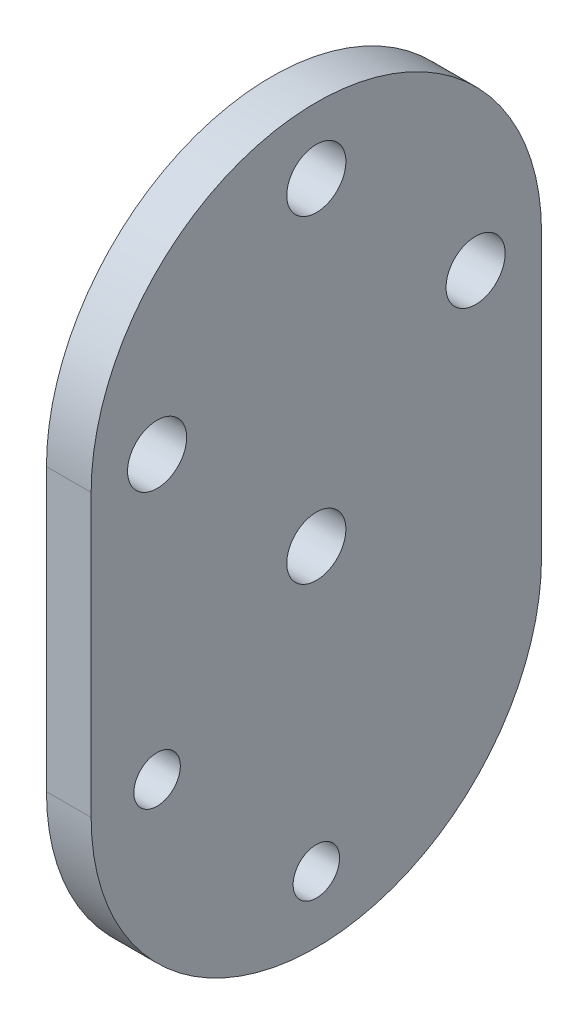
SolidWorks part; units mm, degrees
ref_plane "Front" through (0, 0, 0) normal (0, 0, 1) x (1, 0, 0)
ref_plane "Top" through (0, 0, 0) normal (0, 1, 0) x (1, 0, 0)
ref_plane "Right" through (0, 0, 0) normal (1, 0, 0) x (0, 0, -1)
sketch "Sketch2" plane through (0, 0, 0) normal (1, 0, 0) x (0, 0, -1)
  line L0 (0, -10) -> (0, 10) construction
  line L1 (-16, -10) -> (-16, 10)
  line L2 (16, -10) -> (16, 10)
  arc A0 (-16, -10) -> (16, -10) centre (0, -10) ccw
  arc A1 (16, 10) -> (-16, 10) centre (0, 10) ccw
  circle A2 centre (0, 10) radius 11.3137
  circle A3 centre (0, 21.3137) radius 2.1
  circle A4 centre (0, -1.3137) radius 2.1
  circle A5 centre (11.3137, 10) radius 2.1
  circle A6 centre (-11.3137, 10) radius 2.1
  circle A7 centre (0, -10) radius 11.3137
  circle A8 centre (-11.3137, -10) radius 1.65
  circle A9 centre (0, -21.3137) radius 1.65
  circle A10 centre (11.3137, -10) radius 1.65
  point P2 (0, 0)
extrude "Boss-Extrude1" add sketch "Sketch2" along normal blind 3.175 contours L2 A1 L1 A0 A10 A7 A9 A8 A2 A6 A3 A5 | A7 A2 A5 A3 A6 | A10 A7 A2 A4 A8 A9 | L0 A4 A2 A7 | A4 L0 A7 A2 | A7 A10 | A7 A10 region at (0, -10.5502, 0) region at (0, 0.2133, 2.6256) region at (0, 0.2133, -2.6256) region at (0, 10.3261, 0) region at (0, -10, -11.9919) region at (0, -10, -10.5922) region at (0, 0, 15.3894)
